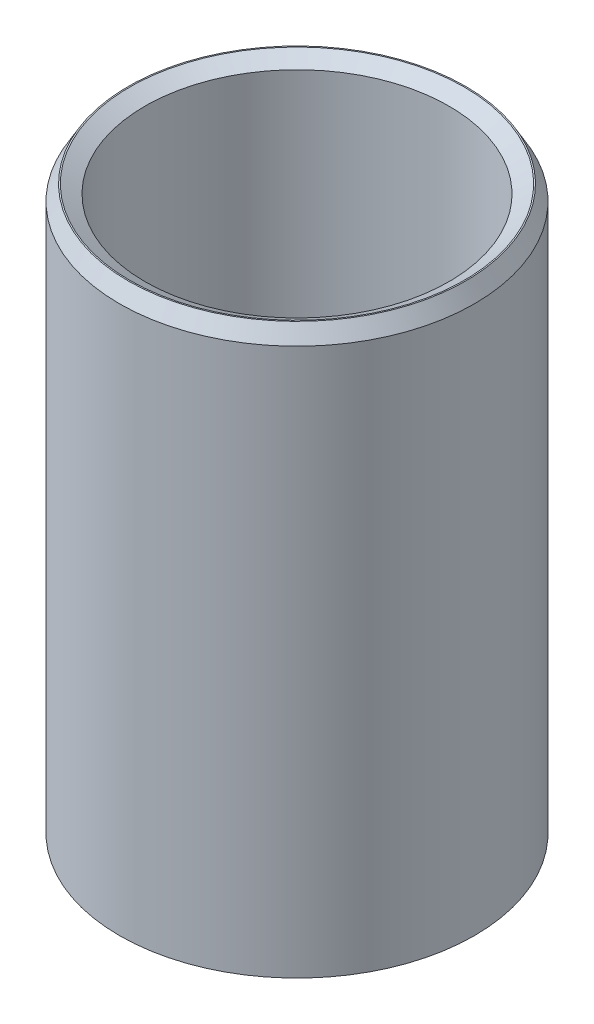
SolidWorks part; units mm, degrees
ref_plane "Front Plane" through (0, 0, 0) normal (0, 0, 1) x (1, 0, 0)
ref_plane "Top Plane" through (0, 0, 0) normal (0, 1, 0) x (1, 0, 0)
ref_plane "Right Plane" through (0, 0, 0) normal (1, 0, 0) x (0, 0, -1)
sketch "Sketch1" plane through (0, 0, 0) normal (0, 1, 0) x (1, 0, 0)
  circle A0 centre (0, 0) radius 27.5
  dimension "SLEEVE_OD" = 55
extrude "Boss-Extrude1" add sketch "Sketch1" along normal blind 88.5257
sketch "Sketch2" plane through (0, 0, 0) normal (0, 1, 0) x (1, 0, 0)
  circle A0 centre (0, 0) radius 23.5595
  dimension "BORE_D" = 47.1189
extrude "Cut-Extrude1" cut sketch "Sketch2" along normal through all
chamfer "Chamfer1" distance 2.3699 angle 30 4 edges at (0, 88.5257, 23.5595) (0, 0, 23.5595) (0, 0, 27.5) (0, 88.5257, 27.5) first distance on face at (0, 88.5257, 23.5595) first distance on face at (0, 0, 23.5595) first distance on face at (0, 88.5257, 27.5)
